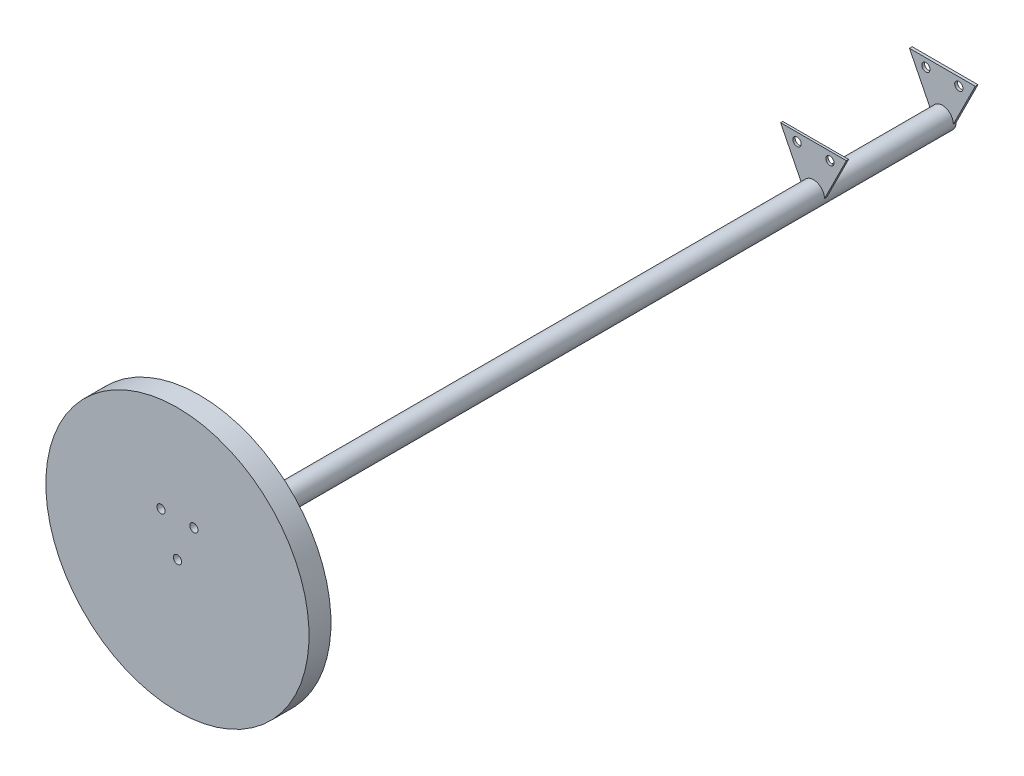
SolidWorks part; units mm, degrees
ref_plane "Front Plane" through (0, 0, 0) normal (0, 0, 1) x (1, 0, 0)
ref_plane "Top Plane" through (0, 0, 0) normal (0, 1, 0) x (1, 0, 0)
ref_plane "Right Plane" through (0, 0, 0) normal (1, 0, 0) x (0, 0, -1)
sketch "Sketch1" plane through (0, 0, 0) normal (1, 0, 0) x (0, 0, -1)
  line L0 (-444.5, 0) -> (444.5, 0)
  line L1 (-444.5, 0) -> (-444.5, 152.4)
  line L2 (-444.5, 152.4) -> (-419.1, 152.4)
  line L3 (-419.1, 152.4) -> (-419.1, 12.7)
  line L4 (-419.1, 12.7) -> (444.5, 12.7)
  line L5 (444.5, 12.7) -> (444.5, 0)
  point P0 (88.9, 0)
  point P4 (0, 0)
  dimension "D1" = 152.4
  dimension "D2" = 25.4
  dimension "D3" = 12.7
  dimension "D4" = 889
  dimension "D5" = 355.6
revolve "OAL Revolve" add sketch "Sketch1" angle 360 about L0
sketch "Sketch3" plane through (0, 0, -444.5) normal (0, 0, -1) x (-1, 0, 0)
  line L0 (12.7, 0) -> (-12.7, 0)
  line L1 (-12.7, 0) -> (-38.1, 50.8)
  line L2 (-38.1, 50.8) -> (38.1, 50.8)
  line L3 (0, 0) -> (0, 152.4) construction
  line L4 (0, 50.8) -> (0, 0) construction
  line L5 (12.7, 0) -> (38.1, 50.8)
  dimension "D1" = 50.8
  dimension "D2" = 38.1
  dimension "D3" = 12.7
extrude "End Tab 1" add sketch "Sketch3" against normal blind 3.175
sketch "Sketch4" plane through (0, 0, -444.5) normal (0, 0, -1) x (-1, 0, 0)
  line L0 (0, 50.8) -> (0, 41.275) construction
  line L1 (38.1, 50.8) -> (-38.1, 50.8) construction
  line L2 (0, 0) -> (0, 152.4) construction
  line L3 (0, 41.275) -> (-19.05, 41.275) construction
  line L4 (0, 41.275) -> (0, 0) construction
  circle A0 centre (-19.05, 41.275) radius 4.7625
  circle A1 centre (19.05, 41.275) radius 4.7625
  circle A2 centre (0, 0) radius 4.7625
  dimension "D3" = 9.525
  dimension "D4" = 9.525
  dimension "D1" = 9.525
  dimension "D2" = 19.05
extrude "End Tab 1 Cut" cut sketch "Sketch4" against normal through all
ref_plane "Plane1" through (0, 0, -292.1) normal (0, 0, -1) x (-1, 0, 0)
sketch "Sketch5" plane through (0, 0, -292.1) normal (0, 0, -1) x (-1, 0, 0)
  line L0 (-38.1, 50.8) -> (-12.7, 0) construction
  line L1 (12.7, 0) -> (38.1, 50.8)
  line L2 (38.1, 50.8) -> (-38.1, 50.8)
  line L3 (-38.1, 50.8) -> (-12.7, 0)
  arc A0 (-12.7, 0) -> (12.7, 0) centre (0, 0) cw
  arc A1 (12.7, 0) -> (-12.7, 0) centre (0, 0) ccw construction
  circle A2 centre (19.05, 41.275) radius 4.7625
  circle A3 centre (-19.05, 41.275) radius 4.7625
  dimension "D1" = 9.525
extrude "Boss-Extrude1" add sketch "Sketch5" along normal blind 2.54
